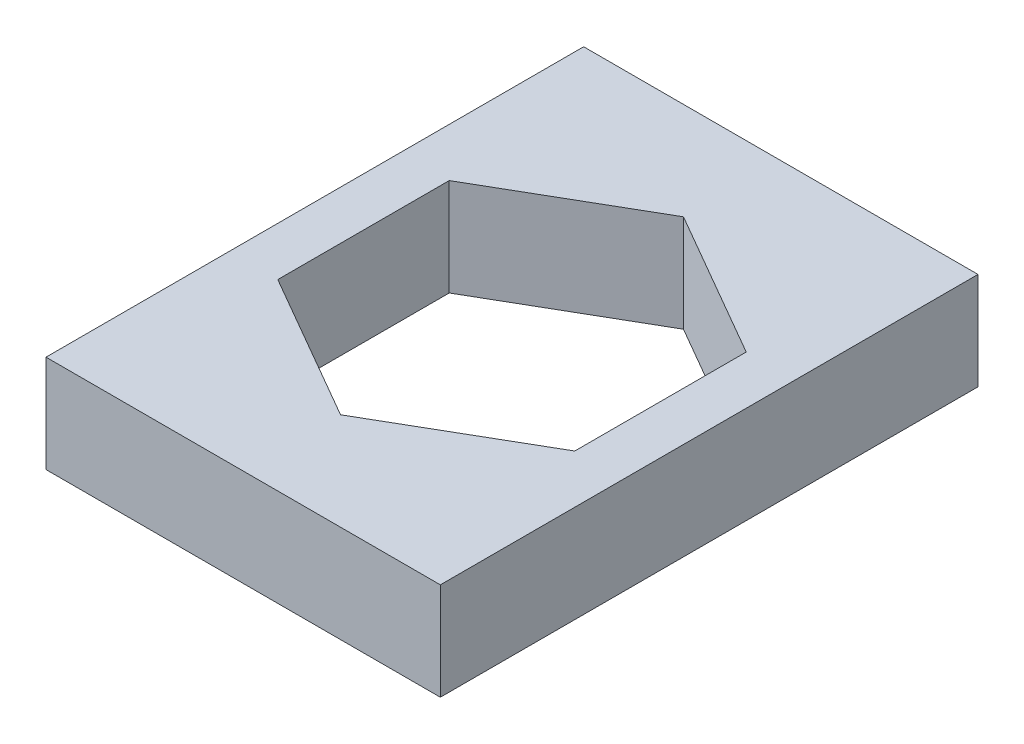
SolidWorks part; units mm, degrees
ref_plane "前视基准面" through (0, 0, 0) normal (0, 0, 1) x (1, 0, 0)
ref_plane "上视基准面" through (0, 0, 0) normal (0, 1, 0) x (1, 0, 0)
ref_plane "右视基准面" through (0, 0, 0) normal (1, 0, 0) x (0, 0, -1)
sketch "草图1" plane through (0, 0, 0) normal (0, 1, 0) x (1, 0, 0)
  line L1 (0, 7.0437) -> (-6.1, 3.5218)
  line L2 (-6.1, 3.5218) -> (-6.1, -3.5218)
  line L3 (-6.1, -3.5218) -> (0, -7.0437)
  line L4 (0, -7.0437) -> (6.1, -3.5218)
  line L5 (6.1, -3.5218) -> (6.1, 3.5218)
  line L6 (6.1, 3.5218) -> (0, 7.0437)
  line L7 (-8.1, 4.6765) -> (-8.1, -4.6765)
  line L10 (8.1, -4.6765) -> (8.1, 4.6765)
  line L12 (-8.1, -4.6765) -> (-8.1, -11.0437)
  line L13 (-8.1, -11.0437) -> (8.1, -11.0437)
  line L14 (8.1, -11.0437) -> (8.1, -4.6765)
  line L15 (-8.1, 4.6765) -> (-8.1, 11.0437)
  line L16 (-8.1, -4.6765) -> (0, -9.3531) construction
  line L17 (0, -9.3531) -> (8.1, -4.6765) construction
  line L18 (-8.1, 11.0437) -> (8.1, 11.0437)
  line L19 (8.1, 11.0437) -> (8.1, 4.6765)
  line L21 (0, 9.3531) -> (-8.1, 4.6765) construction
  line L22 (8.1, 4.6765) -> (0, 9.3531) construction
  circle A0 centre (0, 0) radius 6.1 construction
  dimension "D1" = 12.2
  dimension "D3" = 4
  dimension "D4" = 4
  dimension "D2" = 2
extrude "凸台-拉伸1" add sketch "草图1" along normal blind 4
ref_axis "基准轴1" through (0, 0, 0) along (0, 1, 0)
